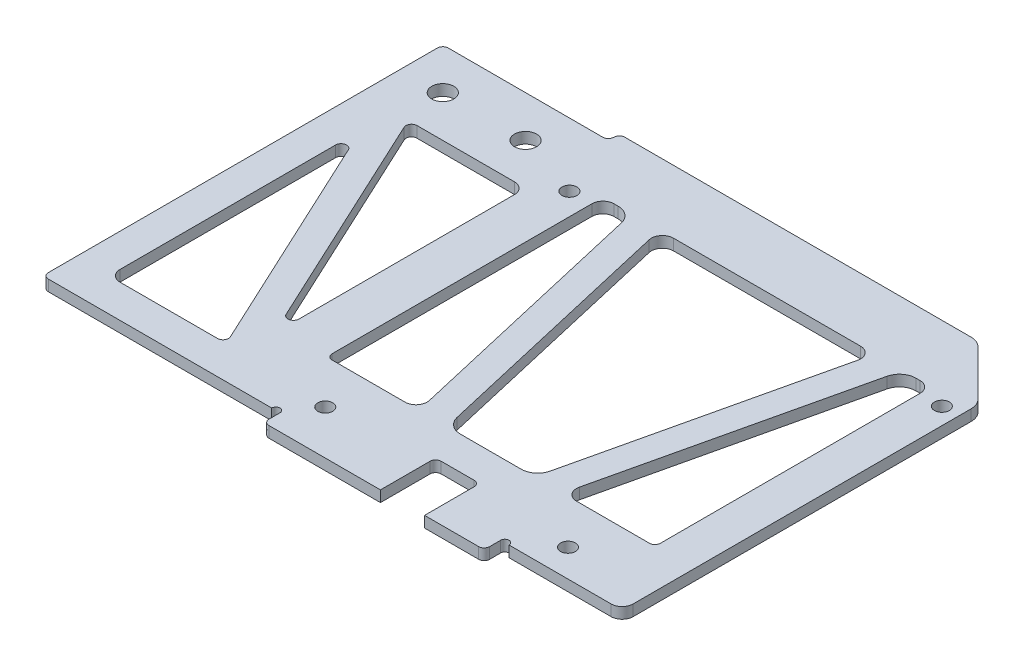
SolidWorks part; units mm, degrees
material "Thornel Mat VMA"
ref_plane "前视基准面" through (0, 0, 0) normal (0, 0, 1) x (1, 0, 0)
ref_plane "上视基准面" through (0, 0, 0) normal (0, 1, 0) x (1, 0, 0)
ref_plane "右视基准面" through (0, 0, 0) normal (1, 0, 0) x (0, 0, -1)
sketch "草图1" plane through (0, 0, 0) normal (0, 1, 0) x (1, 0, 0)
  line L0 (7.5, -7.5) -> (22.5, -7.5) construction
  line L1 (0, 0) -> (30, 0)
  line L2 (0, 0) -> (0, -72.5)
  line L3 (0, -72.5) -> (43, -72.5)
  line L4 (95, 2) -> (105, -8)
  line L5 (83, -72.5) -> (105, -72.5)
  line L6 (40.9897, -42.9201) -> (54.043, -3) construction
  line L7 (40.9897, -42.9201) -> (100.8698, -62.5) construction
  line L8 (100.8698, -62.5) -> (113.9231, -22.5799) construction
  line L9 (54.043, -3) -> (113.9231, -22.5799) construction
  line L11 (30, 0) -> (30, 2)
  line L12 (30, 2) -> (95, 2)
  line L15 (43, -72.5) -> (43, -75.5)
  line L16 (43, -75.5) -> (83, -75.5)
  line L17 (83, -72.5) -> (83, -75.5)
  line L22 (105, -72.5) -> (105, -8)
  circle A0 centre (7.5, -7.5) radius 2
  circle A1 centre (22.5, -7.5) radius 2
  circle A2 centre (40.9897, -42.9201) radius 1.25 construction
  circle A3 centre (100.8698, -62.5) radius 1.25 construction
  circle A4 centre (113.9231, -22.5799) radius 1.25 construction
  circle A5 centre (54.043, -3) radius 1.25 construction
  dimension "D4" = 4
  dimension "D5" = 7.5
  dimension "D6" = 7.5
  dimension "D11" = 2.5
  dimension "D12" = 30
  dimension "D10" = 5
  dimension "D17" = 4
  dimension "D16" = 10
  dimension "D1" = 72.5
  dimension "D2" = 65
  dimension "D3" = 15
  dimension "D7" = 63
  dimension "D8" = 42
  dimension "D9" = 135
  dimension "D13" = 2
  dimension "D14" = 3
  dimension "D15" = 40
  dimension "D18" = 43
  dimension "D19" = 105
extrude "凸台-拉伸1" add sketch "草图1" along normal blind 2
sketch "草图4" plane through (0, 2, 0) normal (0, 1, 0) x (1, 0, 0)
  line L5 (68.2, -3.7432) -> (68.2, -67.5) construction
  line L6 (95, 2) -> (30, 2) construction
  line L23 (34.45, -11.5) -> (101.95, -11.5) construction
  line L24 (34.45, -11.5) -> (46.2, -67.5) construction
  line L25 (46.2, -67.5) -> (90.2, -67.5) construction
  line L26 (0, 0) -> (0, -72.5) construction
  line L28 (43, -75.5) -> (83, -75.5) construction
  line L29 (64.2, -65.5) -> (72.2, -65.5)
  line L30 (64.2, -65.5) -> (64.2, -75.5)
  line L31 (64.2, -75.5) -> (72.2, -75.5)
  line L32 (72.2, -65.5) -> (72.2, -75.5)
  circle A4 centre (34.45, -11.5) radius 1.35
  circle A5 centre (46.2, -67.5) radius 1.35
  circle A8 centre (90.2, -67.5) radius 1.35
  circle A9 centre (101.95, -11.5) radius 1.35
  point P8 (68.2, -11.5)
  point P17 (68.2, -65.5)
  dimension "D7" = 44
  dimension "D8" = 2.7
  dimension "D4" = 68.2
  dimension "D1" = 56
  dimension "D2" = 67.5
  dimension "D3" = 13.5
  dimension "D5" = 8
  dimension "D6" = 2
extrude "切除-拉伸2" cut sketch "草图4" against normal through all
sketch "草图2" plane through (0, 2, 0) normal (0, 1, 0) x (1, 0, 0)
  line L6 (83, -72.5) -> (105, -72.5) construction
  line L9 (30, 0) -> (0, 0) construction
  line L15 (0, -72.5) -> (43, -72.5) construction
  line L17 (6, -15) -> (30, -15)
  line L18 (6, -15) -> (6, -66.5)
  line L19 (6, -66.5) -> (30, -66.5)
  line L20 (30, -15) -> (30, -66.5)
  line L21 (0, 0) -> (0, -72.5) construction
  line L24 (38.45, -9.4353) -> (97.95, -9.4353)
  line L27 (38.45, -9.4353) -> (38.45, -59.5)
  line L40 (30, 2) -> (30, 0) construction
  line L50 (38.45, -59.5) -> (97.95, -59.5)
  line L51 (97.95, -9.4353) -> (97.95, -59.5)
  line L55 (72.2, -65.5) -> (64.2, -65.5) construction
  circle A0 centre (83.75, -72.5) radius 0.75
  circle A1 centre (34.45, -11.5) radius 1.35 construction
  circle A2 centre (42.25, -72.5) radius 0.75
  circle A6 centre (101.95, -11.5) radius 1.35 construction
  dimension "D2" = 4
  dimension "D11" = 1.5
  dimension "D3" = 4
  dimension "D4" = 6
  dimension "D12" = 15
  dimension "D13" = 6
  dimension "D15" = 6
extrude "切除-拉伸1" cut sketch "草图2" against normal through all
sketch "草图3" plane through (0, 2, 0) normal (0, 1, 0) x (1, 0, 0)
  line L0 (6, -15) -> (30, -66.5)
  line L1 (45.7, -7.4353) -> (58.2, -61.5)
  line L2 (97.95, -9.4353) -> (38.45, -9.4353) construction
  line L4 (68.2, -59.5) -> (68.2, -9.4353) construction
  line L5 (38.45, -59.5) -> (97.95, -59.5) construction
  line L6 (90.7, -7.4353) -> (78.2, -61.5)
  dimension "D1" = 2
  dimension "D2" = 2
  dimension "D3" = 45
  dimension "D4" = 20
extrude "拉伸-薄壁1" add sketch "草图3" against normal up to surface (2 mm away) thin up to face at (18, 0, 40.75) thin type mid plane wall 5
fillet "圆角1" radius 1 14 edges at (0, 1, 0) (83, 1, 75.5) (0, 1, 72.5) (43, 1, 75.5) (30, 1, -2) (30, 1, 0) (97.95, 1, 59.5) (38.45, 1, 59.5) (72.2, 1, 65.5) (64.2, 1, 65.5) (30, 1, 60.5815) (8.7581, 1, 15) (6, 1, 20.9185) (27.2419, 1, 66.5)
fillet "圆角3" radius 3 6 edges at (60.3035, 1, 59.5) (76.0965, 1, 59.5) (95, 1, -2) (105, 1, 8) (92.8035, 1, 9.4353) (43.5965, 1, 9.4353)
fillet "圆角2" radius 2 9 edges at (6, 1, 66.5) (30, 1, 15) (55.1716, 1, 59.5) (48.7284, 1, 9.4353) (87.6716, 1, 9.4353) (81.2284, 1, 59.5) (105, 1, 72.5) (97.95, 1, 9.4353) (38.45, 1, 9.4353)
